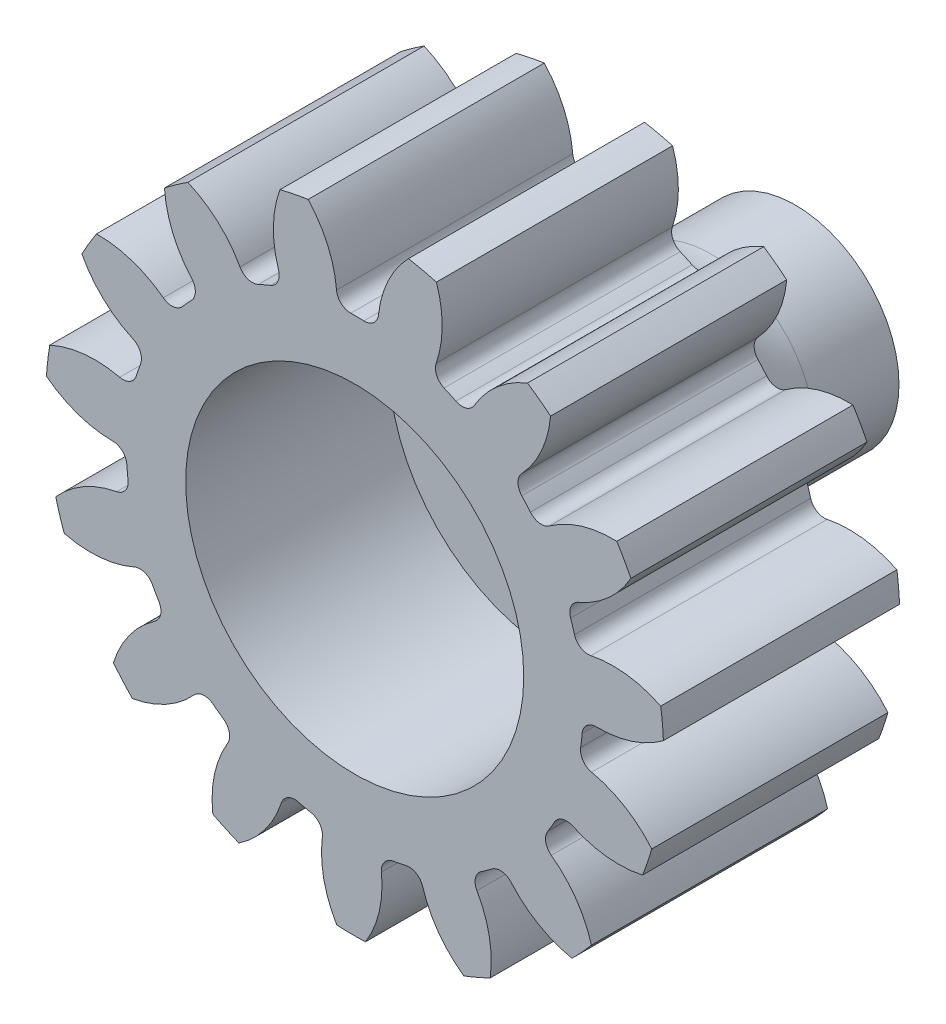
SolidWorks part; units mm, degrees
material "ABS"
ref_plane "Front" through (0, 0, 0) normal (0, 0, 1) x (1, 0, 0)
ref_plane "Top" through (0, 0, 0) normal (0, 1, 0) x (1, 0, 0)
ref_plane "Right" through (0, 0, 0) normal (1, 0, 0) x (0, 0, -1)
sketch "Sketch3" plane through (0, 0, 0) normal (0, 0, 1) x (1, 0, 0)
  circle A0 centre (0, 0) radius 21.59
  dimension "od" = 43.18
extrude "gearBody" add sketch "Sketch3" along normal blind 11
sketch "Sketch2" plane through (0, 0, 0) normal (0, 0, 1) x (1, 0, 0)
  line L0 (0, 0) -> (17.0393, 7.0579) construction
  line L1 (22.0105, -8.0941) -> (0, 0) construction
  line L2 (0, 0) -> (36.3143, 0) construction
  line L3 (19.0486, -0.229) -> (18.5878, -4.1711) construction
  line L5 (18.8182, -2.2) -> (0, 0) construction
  line L7 (0, 0) -> (18.4432, 0) construction
  arc A0 (18.4395, -0.3701) -> (18.0276, -3.8932) centre (0, 0) ccw construction
  arc A1 (21.5666, 1.0048) -> (20.7532, -5.9524) centre (0, 0) ccw construction
  arc A2 (19.0486, -0.229) -> (18.5878, -4.1711) centre (0, 0) ccw construction
  arc A3 (15.7838, -2.3046) -> (15.8898, -1.3984) centre (0, 0) ccw
  arc A4 (22.0105, -8.0941) -> (16.5506, -3.4102) centre (14.9518, -10.798) ccw
  arc A5 (22.0105, -8.0941) -> (23.2839, 2.7987) centre (0, 0) ccw
  arc A6 (23.2839, 2.7987) -> (16.8909, -0.4995) centre (17.0393, 7.0579) cw
  arc A7 (15.8898, -1.3984) -> (16.8909, -0.4995) centre (16.8715, -1.4848) cw
  arc A8 (16.5506, -3.4102) -> (15.7838, -2.3046) centre (16.759, -2.4469) cw
  point P6 (23.2839, 2.7987)
  point P22 (22.0105, -8.0941)
  dimension "baseDia" = 36.8864
  dimension "od" = 43.18
  dimension "pd" = 38.1
  dimension "rd" = 31.9024
  dimension "rFillet" = 0.9855
  dimension "pointX" = 23.2839
  dimension "pointY" = 2.7987
  dimension "CTT" = 3.9421
  dimension "flankCenterAngle" = 22.5
extrude "toothCut" cut sketch "Sketch2" along normal through all
pattern_circular "CirPattern1" count 15 over 360 about axis through (0, 0, 11) along (0, 0, -1) of "toothCut"
scale "Scale1" scale about centroid uniform scaling no x scale factor 0.666667 y scale factor 0.666667 z scale factor 1
sketch "hub1Dia" plane through (0, 0, 0) normal (0, 0, -1) x (-1, 0, 0)
  circle A0 centre (0, 0) radius 12.7
  dimension "hub1Dia" = 25.4
sketch "hub2Dia" plane through (0, 0, 11) normal (0, 0, 1) x (1, 0, 0)
  circle A0 centre (0, 0) radius 12.7
  dimension "hub2dia" = 25.4
sketch "boreDia" plane through (0, 0, 0) normal (0, 0, 1) x (1, 0, 0)
  circle A0 centre (0, 0) radius 7.874
  dimension "boreDia" = 15.748
extrude "bore" cut sketch "boreDia" against normal mid plane 25400
sketch "Sketch4" plane through (0, 0, 0) normal (1, 0, 0) x (0, 0, -1)
  line L0 (9.525, 0) -> (-1.524, 0)
  line L1 (-1.524, 0) -> (-1.524, 7.874)
  line L2 (-1.524, 7.874) -> (0, 7.874)
  line L3 (0, 8.1454) -> (0, 11.133) construction
  line L4 (0, 7.874) -> (0, 10.414)
  line L7 (5.588, 4.826) -> (9.525, 4.826)
  line L8 (9.525, 4.826) -> (9.525, 0)
  line L9 (0, 0) -> (18.4907, 0) construction
  arc A0 (0, 10.414) -> (5.588, 4.826) centre (5.588, 10.414) ccw
  point P15 (7.2078, 12.2601)
  point P16 (0, 15.5858)
  dimension "D2" = 5.588
  dimension "D1" = 15.748
  dimension "D3" = 1.524
  dimension "D5" = 9.652
  dimension "D6" = 9.525
revolve "Revolve1" add sketch "Sketch4" angle 360 about L9
equation "\"Motor_OD\" = 54.4mm"
equation "\"Motor_Length\" = 401mm"
equation "\"Aft_Section_Length\" = 32in"
equation "\"Mid_Coupler_Length\" = 12in"
equation "\"AB_Coupler_OD_Length\"= 1in"
equation "\"AB_Coupling_Section_Length\"= 0.375in"
equation "\"AB_Coupler_Length\"= \"AB_Coupler_OD_Length\" + \"AB_Coupling_Section_Length\" * 2"
equation "\"Cutout_Angle\" = 60"
equation "\"AB_Paddle_Height\" = 0.375in"
equation "\"AB_Coupler_Num_Screws\"= 4"
equation "\"Num_Cutouts\" = 4"
equation "\"AB_Coupler_OD\"= 4.024in"
equation "\"AB_Coupler_ID\"= 3.7in"
equation "\"AB_Coupler_Surface_Diameter\"= 3.899in"
equation "\"AB_Coupling_Screw_Diameter\"= 4.5mm"
equation "\"AB_Central_Bushing_Length\" = 0.75in"
equation "\"Lead_Screw_Dist\" = 2in"
equation "\"Lead_Screw_Diam\" = 0.375in"
equation "\"Lead_Screw_Length\" = \"Mid_Coupler_Length\" + 2*0.375in + 2*0.5in"
equation "\"Paddle_Pin_Offset\" = 0.25in"
equation "\"Paddle_Pin_Radius\" = 2.25*2/3in"
equation "\"Paddle_Gear_OD\" = 3.2in"
equation "\"Fwd_BKHD_From_Top\" = 18in"
equation "\"Body_Tube_OD\"= 4.024in"
equation "\"Body_Tube_ID\"= 3.90in"
equation "\"Coupler_OD\" = 3.899in"
equation "\"Coupler_ID\" = 3.755in"
equation "\"Fwd_Section_Length\" = 20in"
equation "\"Mid_Section_Length\" = 4in"
equation "\"Aft_Upper_Tube_Length\" = 10in"
equation "\"Aft_Lower_Tube_Length\" = 18in"
equation "\"Nosecone_Coupler_Length\" = 5in"
equation "\"Avionics_Bulkhead_Thickness\" = 0.25in"
equation "\"Avionics_Bulkhead_Lip\" = 0.125in"
equation "\"Avionics_Board_Length\" = \"Mid_Coupler_Length\" - 2*\"Avionics_Bulkhead_Lip\""
equation "\"Lead_Screw_Hole_Diam\" = 0.386in"
equation "\"Centering_Ring_Cutout_Dia\"= 1in"
equation "\"Fin_Thickness\" = 0.118in"
equation "\"Airbrakes_Wire_Hole_Dist\" = 1.1*2/3in"
equation "\"Airbrakes_Wire_Hole_Dia\" = 0.25in"
equation "\"Drive_Gear_OD\" = 1.7*2/3in"
equation "\"DB9_Hole_Dist\" = 25mm"
equation "\"DB9_Relief_Width\" = 0.47in"
equation "\"DB9_Relief_Hole_Offset\" = 0.09in"
equation "\"Servo_Gear_Offset\" = 0.5in"
equation "\"Mounting_Bracket_Centerhole_DIA\" = 0.4in"
equation "\"Drive_Gear_Shaft_DIA\" = \"Mounting_Bracket_Centerhole_DIA\" - 0.02in"
equation "\"Drive_Gear_Fillet\" = 0.22in"
equation "\"Drive_Gear_ID\" = 0.62in"
equation "\"M3_Thread_Clearance\" = 3.8mm"
equation "\"M3_Screw_Head_Diam\" = 6.5mm"
equation "\"Screw_Angle\" = 12.5deg"
equation "\"M3_Insert_OD\" = 4.1mm"
equation "\"M4_Insert_OD\" = 5.5mm"
equation "\"Mounting_Hole_Dist\" = 0.15in"
equation "\"Cam_Slot_Length\" = 7mm"
equation "\"Cam_Slot_Width\" = 10mm"
equation "\"D2@Sketch4\"=\"Drive_Gear_Fillet\""
equation "\"D5@Sketch4\"=\"Drive_Gear_Shaft_DIA\""
equation "\"D1@Sketch4\"=\"Drive_Gear_ID\""
